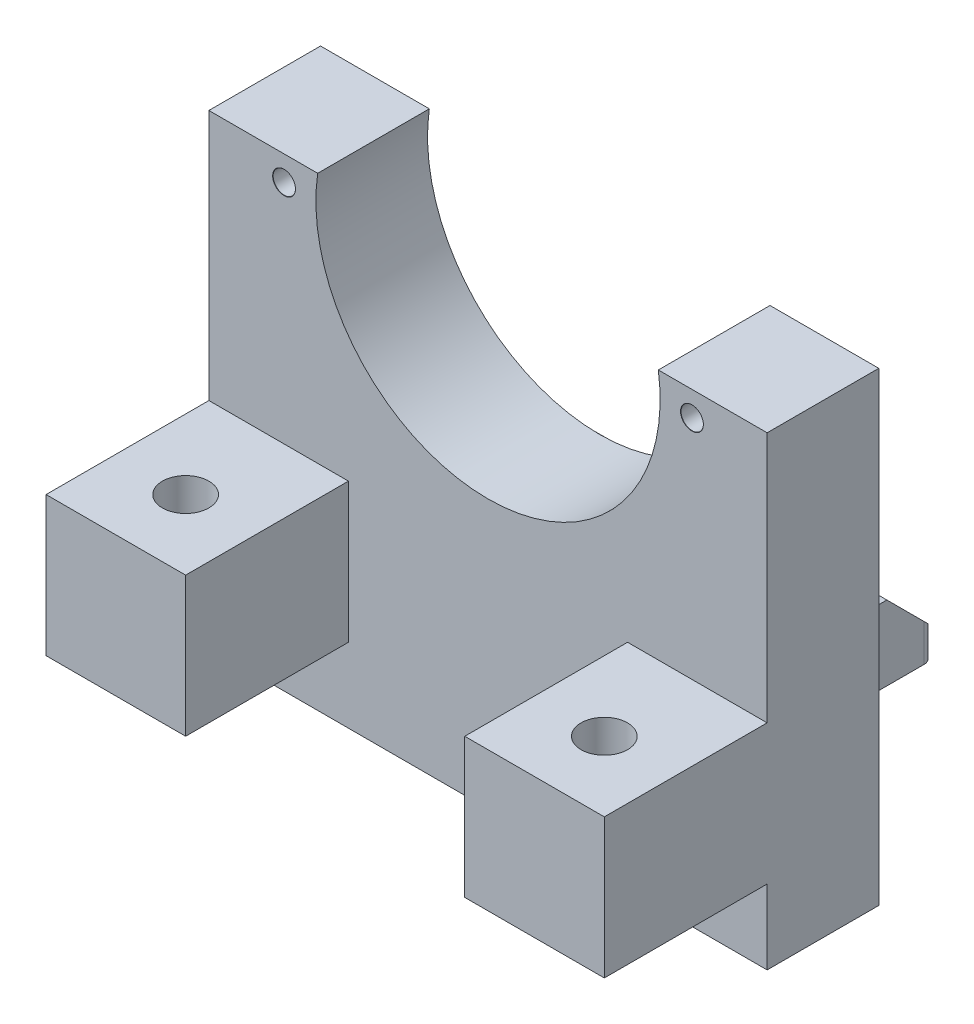
SolidWorks part; units mm, degrees
ref_plane "Front Plane" through (0, 0, 0) normal (0, 0, 1) x (1, 0, 0)
ref_plane "Top Plane" through (0, 0, 0) normal (0, 1, 0) x (1, 0, 0)
ref_plane "Right Plane" through (0, 0, 0) normal (1, 0, 0) x (0, 0, -1)
sketch "Sketch8" plane through (0, 0, 0) normal (0, 1, 0) x (1, 0, 0)
  line L1 (20, 9.75) -> (-20, 9.75)
  line L2 (20, 9.75) -> (20, -9.75)
  line L3 (20, -9.75) -> (-20, -9.75)
  line L4 (-20, 9.75) -> (-20, -9.75)
  line L5 (20, 9.75) -> (-20, -9.75) construction
  line L6 (20, -9.75) -> (-20, 9.75) construction
  point P0 (0, 0)
  dimension "D1" = 19.5
  dimension "D2" = 40
extrude "Boss-Extrude1" add sketch "Sketch8" along normal blind 8
sketch "Sketch10" plane through (0, 8, 0) normal (0, 1, 0) x (1, 0, 0)
  line L1 (8, 8) -> (-8, 8)
  line L2 (8, 8) -> (8, -8)
  line L3 (8, -8) -> (-8, -8)
  line L4 (-8, 8) -> (-8, -8)
  line L5 (8, 8) -> (-8, -8) construction
  line L6 (8, -8) -> (-8, 8) construction
  point P0 (0, 0)
  dimension "D1" = 16
  dimension "D2" = 16
sketch "Sketch16" plane through (0, 0, -9.75) normal (0, 0, -1) x (-1, 0, 0)
  line L0 (-20, 8) -> (-20, 0) construction
  line L1 (-20, 8) -> (20, 8)
  line L2 (-20, 8) -> (-20, 0)
  line L3 (-20, 0) -> (20, 0)
  line L4 (20, 8) -> (20, 0)
  line L5 (-20, 8) -> (20, 8) construction
extrude "Boss-Extrude2" add sketch "Sketch16" along normal blind 17.87
chamfer "Chamfer2" distance 5 angle 45 1 edges at (0, 8, -27.62)
fillet "Fillet1" radius 1 2 edges at (-20, 1.5, -27.62) (20, 1.5, -27.62)
hole_wizard "CBORE for M3 SHCS2" positions "Sketch17" profile "Sketch18" counterbore size "M3" standard "ANSI Metric" end condition through all
sketch "Sketch17" plane through (0, 8, 0) normal (0, 1, 0) x (1, 0, 0)
  point P0 (-8, 8)
  point P3 (8, 8)
sketch "Sketch18" plane through (-8, 8, -8) normal (1, 0, 0) x (0, 0, 1)
  line L0 (0, 0) -> (0, 8)
  line L1 (0, 8) -> (1.7, 8)
  line L3 (1.7, 8) -> (1.7, 3)
  line L4 (3.25, 3) -> (1.7, 3)
  line L5 (3.25, 3) -> (3.25, 0.025)
  line L6 (3.25, 0.025) -> (3.275, 0)
  line L7 (3.275, 0) -> (0, 0)
  line L8 (-3.25, 0.025) -> (-3.275, 0) construction
  line L11 (0, -6.35) -> (0, 107.95) construction
  dimension "Thru Hole Dia." = 3.4
  dimension "Thru Hole Depth" = 8
  dimension "C'Bore Dia." = 6.5
  dimension "C'Bore Depth" = 3
  dimension "Near C'Sink Dia." = 6.55
  dimension "Near C'Sink Angle" = 90
sketch "Sketch19" plane through (0, 0, 9.75) normal (0, 0, 1) x (1, 0, 0)
  line L4 (-20, 0) -> (20, 0)
  line L5 (20, 0) -> (20, 8)
  line L6 (20, 8) -> (-20, 8)
  line L7 (-20, 8) -> (-20, 0)
  line L8 (-20, 0) -> (20, 0)
  line L9 (20, 0) -> (20, 8)
  line L10 (20, 8) -> (-20, 8)
  line L11 (-20, 8) -> (-20, 0)
  dimension "D1" = 0
extrude "Boss-Extrude3" add sketch "Sketch19" along normal blind 0.5
sketch "Sketch20" plane through (0, 0, 10.25) normal (0, 0, 1) x (1, 0, 0)
  line L0 (0, 0) -> (40, 0)
  line L1 (40, 0) -> (40, 50)
  line L2 (40, 50) -> (-20, 50)
  line L3 (-20, 8) -> (-20, 0) construction
  line L4 (-20, 50) -> (-20, 0)
  line L5 (-20, 0) -> (0, 0)
  dimension "D1" = 60
  dimension "D2" = 50
extrude "Boss-Extrude4" add sketch "Sketch20" against normal blind 12
sketch "Sketch21" plane through (0, 0, 10.25) normal (0, 0, 1) x (1, 0, 0)
  line L0 (40, 50) -> (-20, 50) construction
  line L2 (10, 50) -> (10, 0) construction
  line L3 (-20, 0) -> (40, 0) construction
  line L4 (-11.92, 47.34) -> (31.92, 47.34) construction
  point P0 (-11.92, 47.34)
  point P10 (31.92, 47.34)
  dimension "D1" = 2.66
  dimension "D2" = 43.84
hole_wizard "M2 Clearance Hole1" positions "Sketch24" profile "Sketch25" hole size "M2" standard "ANSI Metric" end condition through all
sketch "Sketch24" plane through (0, 0, 10.25) normal (0, 0, 1) x (1, 0, 0)
  point P0 (-11.92, 47.34)
  point P3 (31.92, 47.34)
sketch "Sketch25" plane through (-11.92, 47.34, 10.25) normal (1, 0, 0) x (0, -1, 0)
  line L0 (0, 0) -> (0, 37.87)
  line L1 (0, 37.87) -> (1.2, 37.87)
  line L2 (1.2, 37.87) -> (1.2, 0.025)
  line L3 (1.2, 0.025) -> (1.225, 0)
  line L5 (1.225, 0) -> (0, 0)
  line L6 (-1.2, 0.025) -> (-1.225, 0) construction
  line L11 (0, -6.35) -> (0, 107.95) construction
  dimension "Thru Hole Dia." = 2.4
  dimension "Thru Hole Depth" = 37.87
  dimension "Near C'Sink Dia." = 2.45
  dimension "Near C'Sink Angle" = 90
sketch "Sketch26" plane through (0, 0, 10.25) normal (0, 0, 1) x (1, 0, 0)
  line L0 (-11.92, 47.34) -> (31.92, 47.34) construction
  circle A0 centre (10, 47.34) radius 18.5
  dimension "D1" = 37
extrude "Cut-Extrude2" cut sketch "Sketch26" against normal through all
sketch "Sketch34" plane through (0, 0, 10.25) normal (0, 0, 1) x (1, 0, 0)
  line L0 (-20, 50) -> (-20, 0) construction
  line L1 (-20, 8) -> (-5, 8)
  line L2 (-20, 8) -> (-20, 23)
  line L3 (-20, 23) -> (-5, 23)
  line L4 (-5, 8) -> (-5, 23)
  line L5 (-20, 0) -> (40, 0) construction
  line L6 (10, 0) -> (10, 28.84) construction
  line L7 (40, 23) -> (25, 23)
  line L8 (25, 8) -> (25, 23)
  line L9 (40, 8) -> (25, 8)
  line L10 (40, 8) -> (40, 23)
  arc A0 (-8.3078, 50) -> (28.3078, 50) centre (10, 47.34) ccw construction
  dimension "D1" = 15
  dimension "D2" = 8
  dimension "D3" = 15
extrude "Boss-Extrude5" add sketch "Sketch34" along normal blind 17.5
sketch "Sketch35" plane through (0, 23, 0) normal (0, 1, 0) x (1, 0, 0)
  line L0 (-20, -20.25) -> (30.3, -20.25) construction
  line L3 (-12.5, -27.75) -> (-12.5, -10.25) construction
  line L4 (-5, -27.75) -> (-20, -27.75) construction
  line L5 (-5, -10.25) -> (-20, -10.25) construction
  line L6 (32.5, -27.75) -> (32.5, -10.25) construction
  line L7 (40, -27.75) -> (25, -27.75) construction
  line L8 (40, -10.25) -> (25, -10.25) construction
  circle A0 centre (-12.5, -20.25) radius 2.5
  circle A1 centre (32.5, -20.25) radius 2.5
  dimension "D1" = 5
  dimension "D2" = 7.5
extrude "Cut-Extrude3" cut sketch "Sketch35" against normal blind 15
sketch "Sketch36" plane through (0, 0, 0) normal (1, 0, 0) x (0, 0, -1)
  line L0 (1.75, 28.87) -> (1.75, 8)
  line L1 (1.75, 0) -> (1.75, 50) construction
  line L2 (1.75, 8) -> (22.62, 8)
  line L3 (22.62, 8) -> (1.75, 28.87)
extrude "Boss-Extrude6" add sketch "Sketch36" against normal mid plane 8
